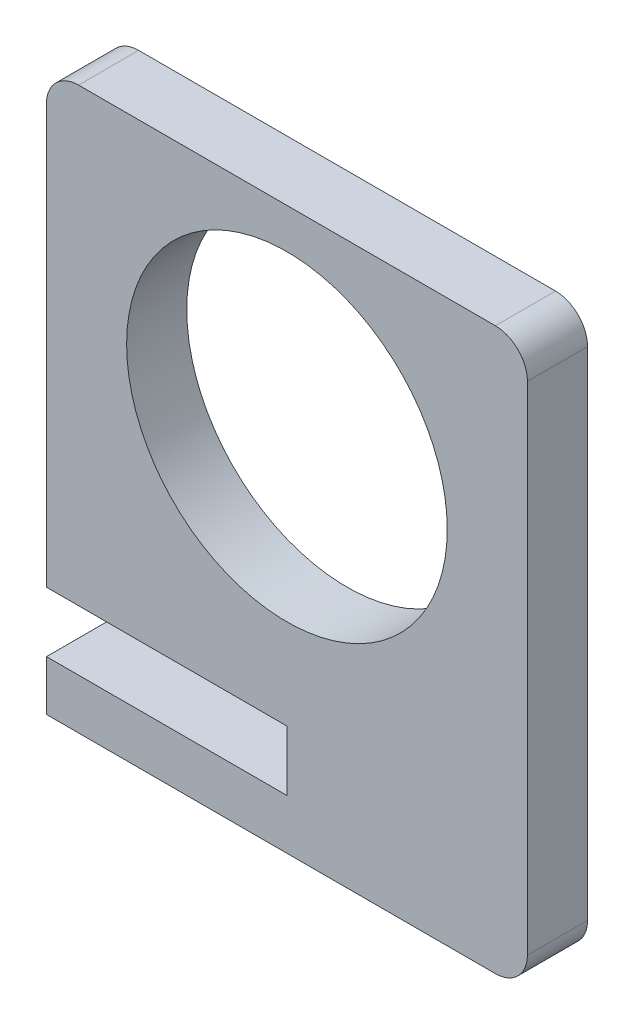
SolidWorks part; units mm, degrees
material "Corrugated Paper"
ref_plane "Front Plane" through (0, 0, 0) normal (0, 0, 1) x (1, 0, 0)
ref_plane "Top Plane" through (0, 0, 0) normal (0, 1, 0) x (1, 0, 0)
ref_plane "Right Plane" through (0, 0, 0) normal (1, 0, 0) x (0, 0, -1)
sketch "Sketch1" plane through (0, 0, 0) normal (0, 0, 1) x (1, 0, 0)
  line L0 (-19.05, 2.3813) -> (-19.05, 6.35)
  line L1 (-19.05, -2.3813) -> (0, -2.3813)
  line L3 (-19.05, 2.3813) -> (0, 2.3813)
  line L4 (0, -2.3813) -> (0, 2.3813)
  line L5 (-19.05, 6.35) -> (19.05, 6.35)
  line L6 (0, 0) -> (19.05, 0) construction
  line L7 (19.05, 6.35) -> (19.05, -6.35)
  line L8 (-19.05, -6.35) -> (19.05, -6.35)
  line L9 (-19.05, -2.3813) -> (-19.05, -6.35)
  line L10 (-19.05, 38.1) -> (19.05, 6.35) construction
  line L11 (-19.05, 6.35) -> (19.05, 6.35)
  line L12 (-19.05, 6.35) -> (-19.05, 38.1)
  line L13 (-19.05, 38.1) -> (19.05, 38.1)
  line L14 (19.05, 6.35) -> (19.05, 38.1)
  line L15 (19.05, 38.1) -> (-19.05, 6.35) construction
  circle A0 centre (0, 22.225) radius 12.7
  dimension "D6" = 25.4
  dimension "D1" = 19.05
  dimension "D2" = 4.7625
  dimension "D3" = 19.05
  dimension "D4" = 12.7
  dimension "D5" = 44.45
extrude "Boss-Extrude1" add sketch "Sketch1" along normal mid plane 4.7625 contours L5 L14 L13 L12 | L6 L4 L1 L9 L8 L7 | L4 L6 L7 L5 L0 L3 region at (2.1981, 0, 0) region at (-18.554, 22.225, 0)
fillet "Fillet1" radius 2.54 3 edges at (19.05, -6.35, 0) (-19.05, 38.1, 0) (19.05, 38.1, 0)
equation "\"D2@Sketch1\" = \"thick\""
equation "\"D1@Boss-Extrude1\"= \"thick\""
equation "\"rodThick\"= 0.1in"
equation "\"thick\"= 3 / 16"
